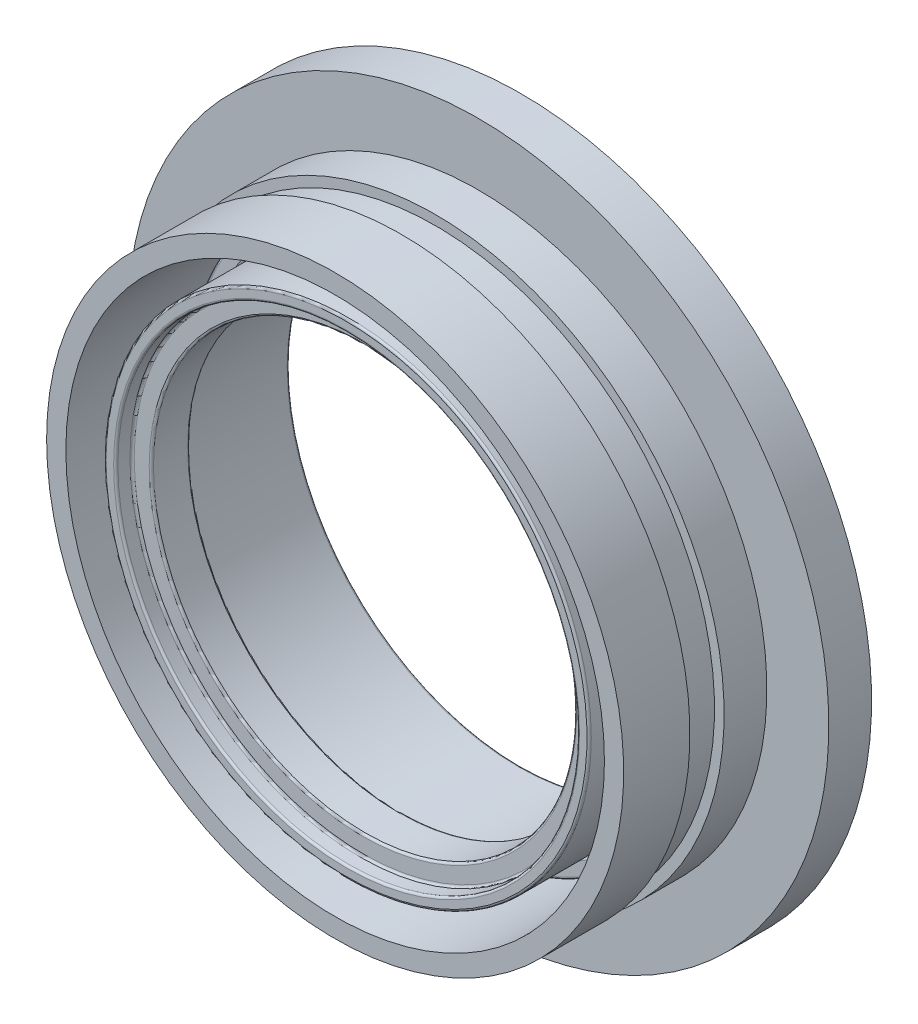
SolidWorks part; units mm, degrees
ref_plane "Front Plane" through (0, 0, 0) normal (0, 0, 1) x (1, 0, 0)
ref_plane "Top Plane" through (0, 0, 0) normal (0, 1, 0) x (1, 0, 0)
ref_plane "Right Plane" through (0, 0, 0) normal (1, 0, 0) x (0, 0, -1)
sketch "Sketch1" plane through (0, 0, 0) normal (0, 1, 0) x (1, 0, 0)
  line L0 (0, 34) -> (0, -30.8421) construction
  line L1 (27, 30.0881) -> (27, 26.0881)
  line L2 (27, 26.0881) -> (26.1, 26.0881)
  line L3 (26.1, 26.0881) -> (26.1, 22.8881)
  line L4 (26.1, 22.8881) -> (27, 22.8881)
  line L5 (27, 22.8881) -> (27, 16.6881)
  line L7 (27, 30.0881) -> (32.8, 30.0881)
  line L8 (32.8, 30.0881) -> (32.8, 34.0881)
  line L10 (25.2, 34.0881) -> (32.8, 34.0881)
  line L16 (22.5, 34) -> (21.8, 34)
  line L17 (21.6, 33.8) -> (21.6, 23.0881)
  line L31 (25.2, 32.6554) -> (25.2, 16.6881)
  line L32 (25.2, 16.6881) -> (27, 16.6881)
  line L37 (21.4, 22.8881) -> (20, 22.8881)
  line L38 (19.8, 22.6881) -> (19.8, 19.4881)
  line L39 (20, 19.2881) -> (21.4, 19.2881)
  line L40 (21.6, 19.0881) -> (21.6, 17.9594)
  line L41 (21.8, 17.7594) -> (22.5, 17.7594)
  line L42 (22.7, 17.9594) -> (22.7, 32.6554)
  line L43 (25.2, 34.0881) -> (24.4, 34.0881)
  line L44 (24.2, 33.8881) -> (24.2, 28.1554)
  line L46 (24.7, 27.6554) -> (24.7, 32.6554)
  line L47 (24.9, 32.8554) -> (25, 32.8554)
  line L48 (24.5, 27.4554) -> (23.4, 27.4554)
  line L49 (23.2, 27.6554) -> (23.2, 32.6554)
  line L50 (23, 32.8554) -> (22.9, 32.8554)
  line L52 (22.5, 34) -> (23.5, 34)
  line L53 (23.7, 33.8) -> (23.7, 28.1554)
  line L54 (23.9, 27.9554) -> (24, 27.9554)
  arc A0 (23.7, 28.1554) -> (23.9, 27.9554) centre (23.9, 28.1554) ccw
  arc A1 (22.5, 17.7594) -> (22.7, 17.9594) centre (22.5, 17.9594) ccw
  arc A2 (21.6, 17.9594) -> (21.8, 17.7594) centre (21.8, 17.9594) ccw
  arc A3 (21.4, 19.2881) -> (21.6, 19.0881) centre (21.4, 19.0881) cw
  arc A4 (19.8, 19.4881) -> (20, 19.2881) centre (20, 19.4881) ccw
  arc A5 (20, 22.8881) -> (19.8, 22.6881) centre (20, 22.6881) ccw
  arc A6 (21.4, 22.8881) -> (21.6, 23.0881) centre (21.4, 23.0881) ccw
  arc A7 (21.8, 34) -> (21.6, 33.8) centre (21.8, 33.8) ccw
  arc A8 (23.5, 34) -> (23.7, 33.8) centre (23.5, 33.8) cw
  arc A9 (22.9, 32.8554) -> (22.7, 32.6554) centre (22.9, 32.6554) ccw
  arc A10 (23.2, 32.6554) -> (23, 32.8554) centre (23, 32.6554) ccw
  arc A11 (23.4, 27.4554) -> (23.2, 27.6554) centre (23.4, 27.6554) cw
  arc A12 (24.5, 27.4554) -> (24.7, 27.6554) centre (24.5, 27.6554) ccw
  arc A13 (24, 27.9554) -> (24.2, 28.1554) centre (24, 28.1554) ccw
  arc A14 (25, 32.8554) -> (25.2, 32.6554) centre (25, 32.6554) cw
  arc A15 (24.7, 32.6554) -> (24.9, 32.8554) centre (24.9, 32.6554) cw
  arc A16 (24.4, 34.0881) -> (24.2, 33.8881) centre (24.4, 33.8881) ccw
  point P9 (0, 0)
  point P10 (0, 0)
  point P25 (0, 0)
  point P36 (0, 0)
  point P37 (0, 0)
  point P38 (0, 0)
  point P49 (19.8, 22.8881)
  point P52 (21.6, 22.8881)
  point P55 (21.6, 34)
  point P74 (22.8122, 23.8157)
  point P75 (0, 0)
  dimension "D14" = 0.2
  dimension "D1" = 4
  dimension "D2" = 4
  dimension "D3" = 3.2
  dimension "D4" = 0.9
  dimension "D5" = 1.8
  dimension "D6" = 1.8
  dimension "D7" = 0.9
  dimension "D8" = 0.5
  dimension "D9" = 7.6
  dimension "D10" = 0.5
  dimension "D11" = 0.5
  dimension "D12" = 0.5
  dimension "D13" = 0.5
  dimension "D15" = 6.2
  dimension "D16" = 4.5
  dimension "D17" = 0.5
  dimension "D18" = 27
revolve "Revolve1" add sketch "Sketch1" angle 360 about L0
